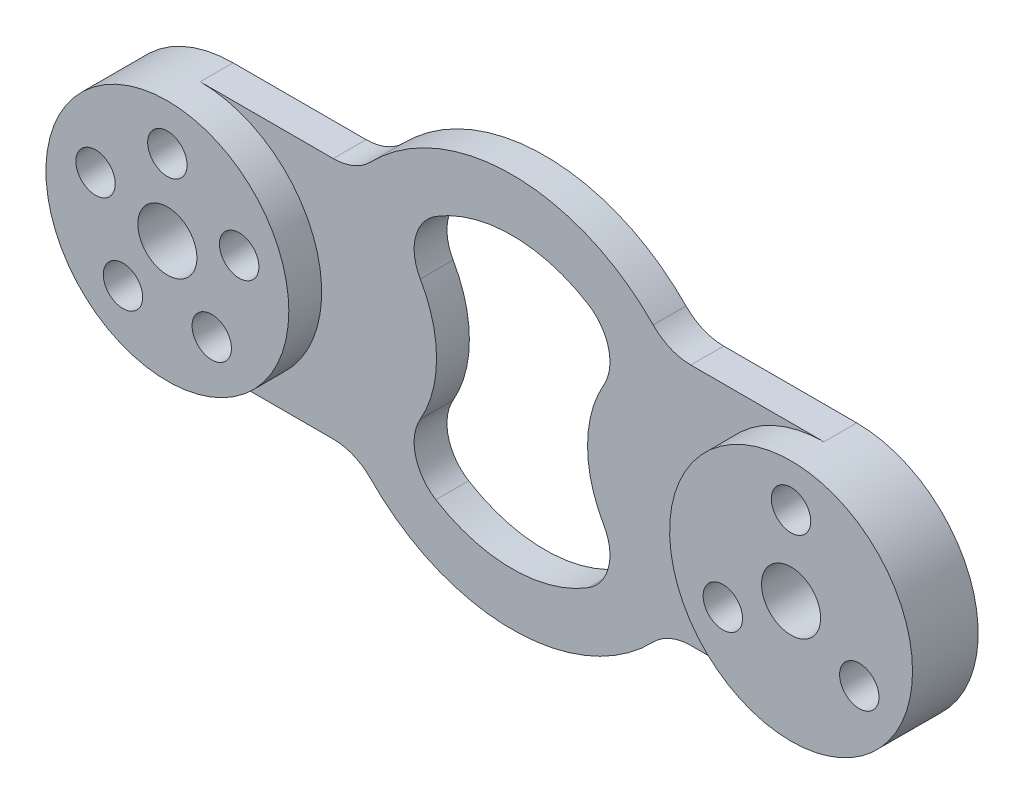
SolidWorks part; units mm, degrees
ref_plane "Спереди" through (0, 0, 0) normal (0, 0, 1) x (1, 0, 0)
ref_plane "Сверху" through (0, 0, 0) normal (0, 1, 0) x (1, 0, 0)
ref_plane "Справа" through (0, 0, 0) normal (1, 0, 0) x (0, 0, -1)
sketch "Эскиз1" plane through (0, 0, 0) normal (0, 0, 1) x (1, 0, 0)
  line L0 (-233.9704, 0) -> (322.9298, 0) construction
  line L1 (-95, 37) -> (-54.4702, 37)
  line L2 (95, 37) -> (54.4702, 37)
  line L3 (95, -37) -> (54.4702, -37)
  line L4 (-95, -37) -> (-54.4702, -37)
  line L5 (-95, 0) -> (-95, 37) construction
  line L6 (95, 0) -> (95, 37) construction
  arc A0 (-43.0028, -41.8421) -> (43.0028, -41.8421) centre (0, 0) ccw
  circle A1 centre (95, 0) radius 37
  circle A2 centre (-95, 0) radius 37
  arc A3 (23.21, 37.3804) -> (-23.21, 37.3804) centre (0, 0) ccw
  arc A4 (-27.9515, -18.4903) -> (-27.9515, 18.4903) centre (-60, 0) ccw
  arc A5 (-54.4702, 37) -> (-43.0028, 41.8421) centre (-54.4702, 53) ccw
  arc A6 (-23.21, -37.3804) -> (23.21, -37.3804) centre (0, 0) ccw
  arc A7 (27.9515, 18.4903) -> (27.9515, -18.4903) centre (60, 0) ccw
  arc A8 (-23.21, 37.3804) -> (-27.9515, 18.4903) centre (-15.825, 25.4867) ccw
  arc A9 (27.9515, 18.4903) -> (23.21, 37.3804) centre (15.825, 25.4867) ccw
  arc A10 (-27.9515, -18.4903) -> (-23.21, -37.3804) centre (-15.825, -25.4867) ccw
  arc A11 (23.21, -37.3804) -> (27.9515, -18.4903) centre (15.825, -25.4867) ccw
  arc A12 (43.0028, 41.8421) -> (54.4702, 37) centre (54.4702, 53) ccw
  arc A13 (-43.0028, -41.8421) -> (-54.4702, -37) centre (-54.4702, -53) ccw
  arc A14 (54.4702, -37) -> (43.0028, -41.8421) centre (54.4702, -53) ccw
  circle A16 centre (-95, 0) radius 23
  circle A17 centre (-95, 0) radius 9
  circle A18 centre (-95, 23) radius 6
  circle A19 centre (-73.1257, 7.1074) radius 6
  circle A20 centre (-81.4809, -18.6074) radius 6
  circle A21 centre (-108.5191, -18.6074) radius 6
  circle A22 centre (-116.8743, 7.1074) radius 6
  circle A23 centre (95, 0) radius 9
  circle A24 centre (95, 0) radius 24
  circle A25 centre (95, 24) radius 6
  circle A26 centre (115.7846, -12) radius 6
  circle A27 centre (74.2154, -12) radius 6
  arc A29 (43.0028, 41.8421) -> (-43.0028, 41.8421) centre (0, 0) ccw
  point P53 (-95, 0)
  point P63 (95, 0)
  dimension "D1" = 120
  dimension "D2" = 74
  dimension "D3" = 74
  dimension "D6" = 88
  dimension "D7" = 16
  dimension "D8" = 14
  dimension "D9" = 37
  dimension "D10" = 37
  dimension "D11" = 14
  dimension "D12" = 14
  dimension "D13" = 14
  dimension "D14" = 16
  dimension "D15" = 16
  dimension "D16" = 16
  dimension "D17" = 5
  dimension "D19" = 12
  dimension "D20" = 18
  dimension "D21" = 3
  dimension "D23" = 12
  dimension "D24" = 18
  dimension "D4" = 190
  dimension "D5" = 95
  dimension "D18" = 23
  dimension "D22" = 24
extrude "Бобышка-Вытянуть1" add sketch "Эскиз1" along normal blind 10 contours A12 A29 A5 L1 A2 L4 A13 A0 A14 L3 A1 L2 A11 A6 A10 A4 A8 A3 A9 A7 region at (-74.7351, 34.7528, 0)
extrude "Бобышка-Вытянуть2" add sketch "Эскиз1<3>" along normal blind 20 contours A2 A22 A16 A18 A19 A20 A21 | A22 A16 A21 A20 A19 A18 A17 | A1 A27 A24 A25 A26 | A27 A24 A26 A25 A23 region at (-69.577, 25.423, 0) region at (120.423, 25.423, 0) region at (-73.928, -7.4642, 0) region at (118.1096, -3.1735, 0)
sketch "Эскиз1<3>" plane through (0, 0, 0) normal (0, 0, 1) x (1, 0, 0) same geometry as "Эскиз1"
